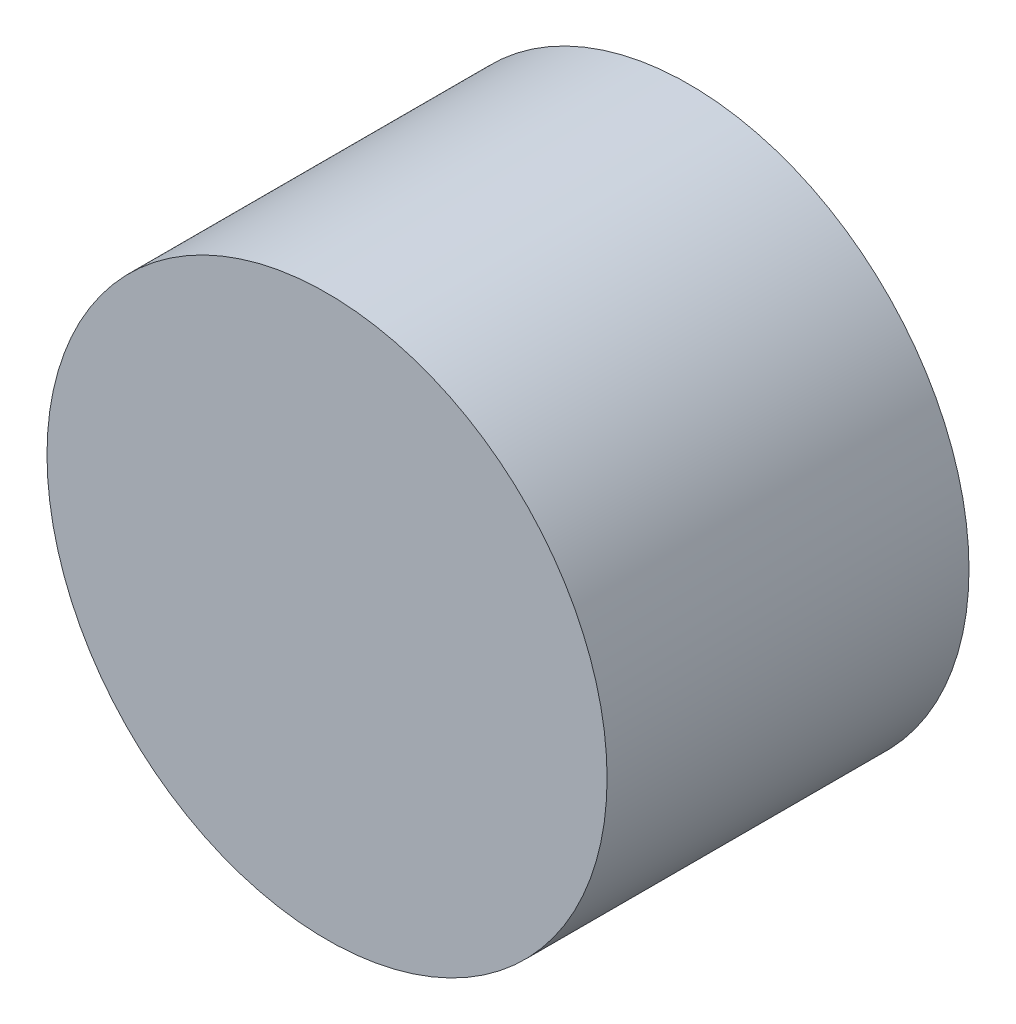
SolidWorks part; units mm, degrees
ref_plane "Front Plane" through (0, 0, 0) normal (0, 0, 1) x (1, 0, 0)
ref_plane "Top Plane" through (0, 0, 0) normal (0, 1, 0) x (1, 0, 0)
ref_plane "Right Plane" through (0, 0, 0) normal (1, 0, 0) x (0, 0, -1)
sketch "Sketch1" plane through (0, 0, 0) normal (0, 0, 1) x (1, 0, 0)
  circle A0 centre (0, 0) radius 32.5
extrude "Boss-Extrude1" add sketch "Sketch1" along normal blind 42
cosmetic thread "Cosmetic Thread1" parameters "D1"=25, "D2"=59.61
sketch "Sketch2" plane through (0, 0, 42) normal (0, 0, 1) x (1, 0, 0)
  circle A0 centre (0, 0) radius 30
  circle A2 centre (0, 0) radius 32.5
extrude "Boss-Extrude5" add sketch "Sketch2" along normal blind 3 from offset 28 offset against normal yes
